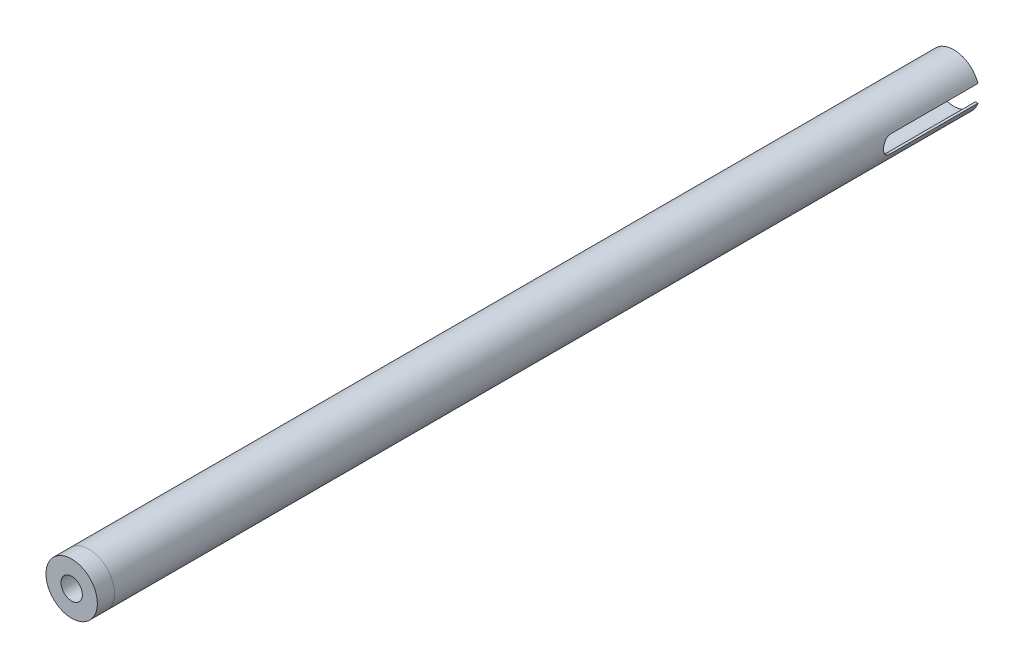
SolidWorks part; units mm, degrees
material "AISI 4130 Steel, normalized at 870C"
ref_plane "Front Plane" through (0, 0, 0) normal (0, 0, 1) x (1, 0, 0)
ref_plane "Top Plane" through (0, 0, 0) normal (0, 1, 0) x (1, 0, 0)
ref_plane "Right Plane" through (0, 0, 0) normal (1, 0, 0) x (0, 0, -1)
sketch "Axis" plane through (0, 0, 0) normal (0, 1, 0) x (1, 0, 0)
  line L0 (0, 0) -> (0, 326.9114) construction
  line L1 (0, 0) -> (0, -28.575) construction
  line L2 (0, 326.9114) -> (-9.525, 326.9114) construction
  line L3 (0, 361.4135) -> (-10.3187, 324.0363) construction
  dimension "D1" = 28.575
  dimension "D2" = 9.525
sketch "Sketch1" plane through (0, 0, 0) normal (0, 0, 1) x (1, 0, 0)
  line L0 (-9.525, 0) -> (9.525, 0) construction
  line L1 (-8.9803, 3.175) -> (8.9803, 3.175)
  line L2 (-8.9803, -3.175) -> (8.9803, -3.175)
  circle A0 centre (0, 0) radius 9.525
  circle A1 centre (0, 0) radius 8.636
  circle A2 centre (0, 0) radius 3.9688
  dimension "D1" = 19.05
  dimension "D3" = 7.9375
  dimension "D2" = 0.889
  dimension "D4" = 6.35
extrude "Threaded insert 1-1" add sketch "Sketch1" against normal blind 6.35 contours A2 L1 A1 | A1 L1 A0 | A2 L0 A1 L1 | A1 L0 A0 L1 | L0 A1 L2 A0 | L0 A2 L2 A1 | A2 L2 A1 | A1 L2 A0 | L0 A1 L2 A2 | L0 A0 L2 A1 | A0 L0 A1 L1 | A1 L0 A2 L1 region at (5.9465, 1.6355, 0) region at (5.9465, -1.6355, 0) region at (8.8881, 1.6046, 0) region at (8.8881, -1.6046, 0) region at (-5.9465, -1.6355, 0) region at (-5.9465, 1.6355, 0) region at (0, 5.5139, 0) region at (0, -5.5139, 0) region at (0, 8.8265, 0) region at (8.5057, -3.3655, 0) region at (-8.8881, -1.6046, 0) region at (-8.8881, 1.6046, 0)
extrude "Threaded insert 1-2" add sketch "Sketch1<3>" against normal blind 9.525 from surface contours A2 L1 A1 | A2 L0 A1 L1 | L0 A2 L2 A1 | A2 L2 A1 | L0 A1 L2 A2 | A1 L0 A2 L1 region at (5.9465, 1.6355, 0) region at (5.9465, -1.6355, 0) region at (-5.9465, -1.6355, 0) region at (-5.9465, 1.6355, 0) region at (0, 5.5139, 0) region at (0, -5.5139, 0) starting at face at (9.525, 0, -6.35)
sketch "Sketch1<3>" plane through (0, 0, 0) normal (0, 0, 1) x (1, 0, 0) same geometry as "Sketch1"
extrude "A-arm tube" add sketch "Sketch1<4>" against normal up to vertex (326.9114 mm away) from surface separate body contours A1 L1 A0 | A1 L0 A0 L1 | L0 A1 L2 A0 | A1 L2 A0 | L0 A0 L2 A1 | A0 L0 A1 L1 region at (8.8881, 1.6046, 0) region at (8.8881, -1.6046, 0) region at (0, 8.8265, 0) region at (8.5057, -3.3655, 0) region at (-8.8881, -1.6046, 0) region at (-8.8881, 1.6046, 0) up to point (0, 0, -326.9114) starting at face at (8.636, 0, -6.35)
sketch "Sketch1<4>" plane through (0, 0, 0) normal (0, 0, 1) x (1, 0, 0) same geometry as "Sketch1"
extrude "Apex slot" cut sketch "Sketch1<5>" along normal blind 35.56 from surface contours A0 L0 A1 L1 | L0 A0 L2 A1 | A1 L0 A0 L1 | L0 A1 L2 A0 region at (8.8881, 1.6046, 0) region at (8.8881, -1.6046, 0) region at (-8.8881, -1.6046, 0) region at (-8.8881, 1.6046, 0) starting at face at (8.636, 0, -326.9114)
sketch "Sketch1<5>" plane through (0, 0, 0) normal (0, 0, 1) x (1, 0, 0) same geometry as "Sketch1"
fillet "Fillet1" radius 3.175 4 edges at (-8.5057, 3.175, -291.3514) (-8.5057, -3.175, -291.3514) (8.5057, -3.175, -291.3514) (8.5057, 3.175, -291.3514)
equation "\"tube diameter\"= 3 / 4"
equation "\"tube thickness\"= .035"
equation "\"apex thickness\"= .25"
equation "\"tube slot\"= 1.4"
equation "\"D1@Sketch1\"=\"tube diameter\""
equation "\"D2@Sketch1\"=\"tube thickness\""
equation "\"threaded insert hole\"= .3125"
equation "\"D3@Sketch1\"=\"threaded insert hole\""
equation "\"D4@Sketch1\"=\"apex thickness\""
equation "\"D1@Apex slot\" = \"tube slot\""
equation "\"D1@Fillet1\"=\"apex thickness\"/2"
equation "\"D2@Axis\"=\"tube diameter\"/2"
